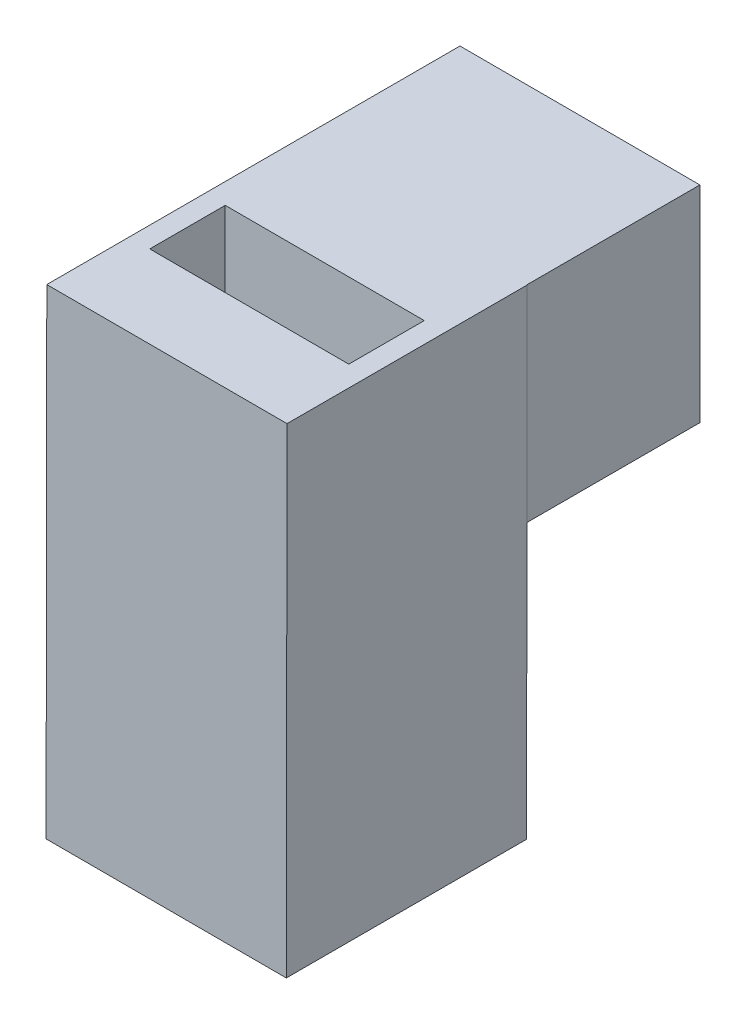
SolidWorks part; units mm, degrees
ref_plane "Front" through (0, 0, 0) normal (0, 0, 1) x (1, 0, 0)
ref_plane "Top" through (0, 0, 0) normal (0, 1, 0) x (1, 0, 0)
ref_plane "Right" through (0, 0, 0) normal (1, 0, 0) x (0, 0, -1)
sketch "Sketch3" plane through (0, 96.8586, 4.3621) normal (-0.0014, -1, 0) x (1, -0.0014, 0)
  line L1 (-8.75, -9.7077) -> (8.75, -9.7077)
  line L2 (-8.75, -9.7077) -> (-8.75, 7.7923)
  line L3 (-8.75, 7.7923) -> (8.75, 7.7923)
  line L4 (8.75, -9.7077) -> (8.75, 7.7923)
  line L5 (-8.75, -9.7077) -> (8.75, 7.7923) construction
  line L6 (-8.75, 7.7923) -> (8.75, -9.7077) construction
  circle A0 centre (0, -0.9577) radius 6.75
  circle A1 centre (0, -0.9577) radius 8.75 construction
  dimension "D1" = 13.5
  dimension "D2" = 2
extrude "Boss-Extrude2" add sketch "Sketch3" along normal blind 20 separate body
sketch "Sketch1" plane through (0, 0, -5.3455) normal (0, 0, 1) x (1, 0, 0)
  line L0 (-2.24, 103.1286) -> (2.24, 103.1286)
  line L2 (-8.7281, 96.8711) -> (8.75, 96.8461)
  line L3 (-8.7281, 96.8711) -> (-8.7281, 106.8586)
  line L4 (-8.7281, 106.8586) -> (8.75, 106.8586)
  line L5 (8.75, 96.8461) -> (8.75, 106.8586)
  line L6 (-8.7281, 96.8711) -> (8.75, 106.8586) construction
  line L7 (-8.7281, 106.8586) -> (8.75, 96.8461) construction
  line L13 (8.75, 96.8461) -> (-8.75, 96.8711) construction
  line L14 (8.75, 96.8461) -> (-8.75, 96.8711) construction
  arc A0 (-2.24, 103.1286) -> (2.24, 103.1286) centre (0, 101.8586) ccw
  circle A2 centre (0, 101.8586) radius 1.5 construction
  arc A3 (2.24, 103.1286) -> (-2.24, 103.1286) centre (0, 101.8586) ccw construction
  circle A4 centre (0, 101.8586) radius 5 construction
  dimension "D1" = 5.15
  dimension "D3" = 10
  dimension "D2" = 4.48
extrude "Boss-Extrude1" add sketch "Sketch1" against normal blind 12.6
sketch "Sketch4" plane through (-0.0693, 96.8587, 0) normal (-0.0014, -1, 0) x (-1, 0.0014, 0)
  line L1 (-7.3193, -6.1545) -> (7.1807, -6.1545)
  line L2 (-7.3193, -6.1545) -> (-7.3193, -0.6545)
  line L3 (-7.3193, -0.6545) -> (7.1807, -0.6545)
  line L4 (7.1807, -6.1545) -> (7.1807, -0.6545)
  line L5 (-7.3193, -6.1545) -> (7.1807, -0.6545) construction
  line L6 (-7.3193, -0.6545) -> (7.1807, -6.1545) construction
  line L10 (-8.8193, 5.3455) -> (-8.8193, -12.1545)
  line L11 (8.6807, 5.3455) -> (-8.8193, 5.3455)
  line L12 (8.6807, -12.1545) -> (8.6807, 5.3455)
  line L13 (-8.8193, -12.1545) -> (8.6807, -12.1545)
  line L14 (6.9307, -0.9045) -> (-7.0693, -0.9045) construction
  line L15 (-7.0693, -0.9045) -> (-7.0693, -5.9045) construction
  line L16 (-7.0693, -5.9045) -> (6.9307, -5.9045) construction
  line L17 (6.9307, -5.9045) -> (6.9307, -0.9045) construction
  line L18 (-8.8193, 5.3455) -> (-8.8193, -12.1545)
  line L19 (8.6807, 5.3455) -> (-8.8193, 5.3455)
  line L20 (8.6807, -12.1545) -> (8.6807, 5.3455)
  line L21 (-8.8193, -12.1545) -> (8.6807, -12.1545)
  circle A2 centre (-0.0693, -3.4045) radius 6.75 construction
  circle A3 centre (-0.0693, -3.4045) radius 6.75 construction
  dimension "D1" = 0.25
  dimension "D2" = 0.25
  dimension "D3" = 0.25
  dimension "D4" = 0.25
  dimension "D5" = 0
extrude "Boss-Extrude3" add sketch "Sketch4" against normal blind 15
sketch "Sketch2" plane through (0, 0, -17.9455) normal (0, 0, -1) x (-1, 0, 0)
  line L0 (-8.75, 106.8586) -> (8.7281, 106.8586) construction
  line L1 (-8.75, 96.8461) -> (-8.75, 106.8586) construction
  circle A0 centre (0, 101.8586) radius 2.575
  dimension "D1" = 5.15
  dimension "D2" = 5
  dimension "D3" = 8.75
extrude "Cut-Extrude1" cut sketch "Sketch2" against normal blind 5
sketch "Sketch5" plane through (0, 0, -17.9455) normal (0, 0, -1) x (-1, 0, 0)
  line L1 (-1.5906, 103.8836) -> (1.5906, 103.8836)
  line L2 (0, 103.8836) -> (0, 99.2836) construction
  line L4 (1.5906, 103.8836) -> (-1.5906, 103.8836)
  arc A0 (-1.5906, 103.8836) -> (1.5906, 103.8836) centre (0, 101.8586) ccw
  arc A2 (1.5906, 103.8836) -> (-1.5906, 103.8836) centre (0, 101.8586) ccw construction
  circle M7 centre (0, 101.8586) radius 2.575
  dimension "D1" = 5.15
  dimension "D2" = 4.6
extrude "Cut-Extrude2" cut sketch "Sketch5" against normal up to surface (18.6 mm away) contours L1 M7 region at (0, 101.722, -17.9455) up to face at (0.0072, 101.8586, 0.6545)
sketch "Sketch6" plane through (0, 106.8586, 0) normal (0, 1, 0) x (1, 0, 0)
  line L1 (-8.7281, 17.9455) -> (8.75, 17.9455)
  line L2 (-8.7281, 17.9455) -> (-8.7281, 5.3455)
  line L3 (-8.7281, 5.3455) -> (8.75, 5.3455)
  line L4 (8.75, 17.9455) -> (8.75, 5.3455)
extrude "Boss-Extrude4" add sketch "Sketch6" along normal up to surface (4.9875 mm away) up to face at (0.0215, 111.8586, 3.4045)
